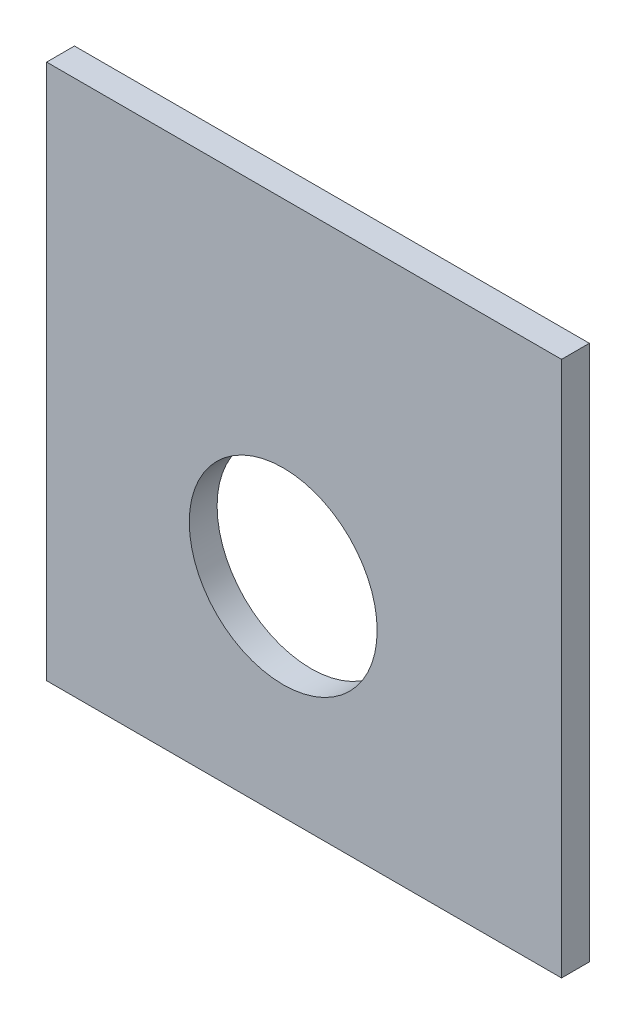
SolidWorks part; units mm, degrees
ref_plane "Plano frontal" through (0, 0, 0) normal (0, 0, 1) x (1, 0, 0)
ref_plane "Plano superior" through (0, 0, 0) normal (0, 1, 0) x (1, 0, 0)
ref_plane "Plano direito" through (0, 0, 0) normal (1, 0, 0) x (0, 0, -1)
sketch "Esboço1" plane through (0, 0, 0) normal (0, 0, 1) x (1, 0, 0)
  line L1 (-86.1657, 44.0263) -> (-12.1657, 44.0263)
  line L2 (-86.1657, 44.0263) -> (-86.1657, -32.9737)
  line L3 (-86.1657, -32.9737) -> (-12.1657, -32.9737)
  line L4 (-12.1657, 44.0263) -> (-12.1657, -32.9737)
  dimension "D1" = 77
  dimension "D2" = 74
extrude "Ressalto-extrusão1" add sketch "Esboço1" along normal blind 4
sketch "Esboço2" plane through (0, 0, 4) normal (0, 0, 1) x (1, 0, 0)
  circle A0 centre (-52.1657, -2.9737) radius 13.5
  dimension "D1" = 27
  dimension "D2" = 34
  dimension "D3" = 30
extrude "Corte-extrusão1" cut sketch "Esboço2" against normal blind 4 and the other way blind 4
